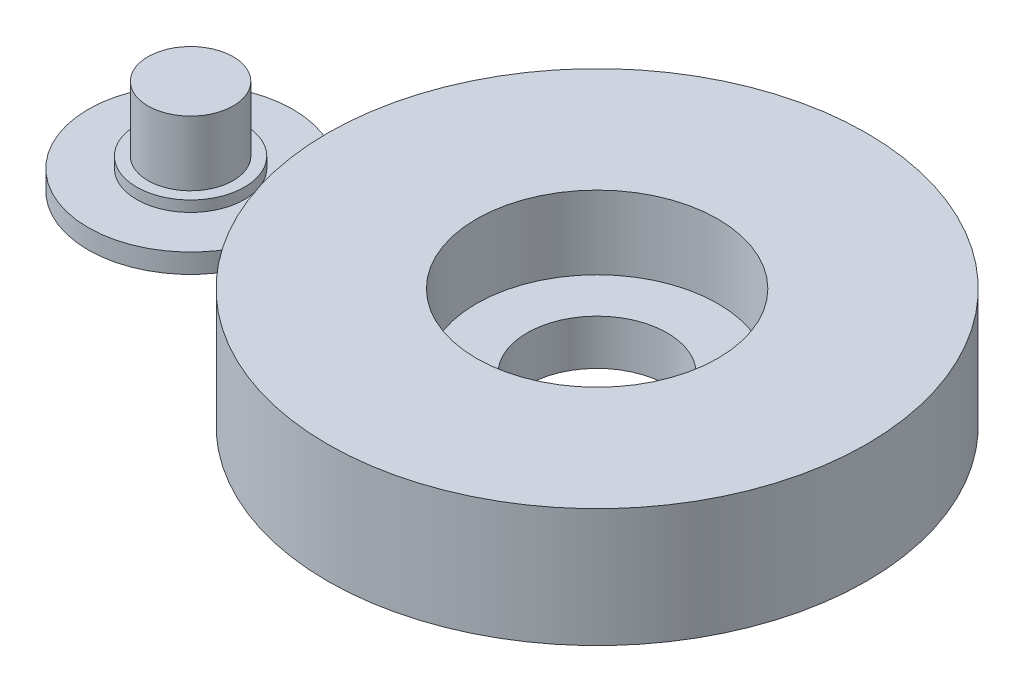
SolidWorks part; units mm, degrees
ref_plane "Front Plane" through (0, 0, 0) normal (0, 0, 1) x (1, 0, 0)
ref_plane "Top Plane" through (0, 0, 0) normal (0, 1, 0) x (1, 0, 0)
ref_plane "Right Plane" through (0, 0, 0) normal (1, 0, 0) x (0, 0, -1)
sketch "Sketch1" plane through (0, 0, 0) normal (0, 1, 0) x (1, 0, 0)
  circle A0 centre (0, 0) radius 9.5
  dimension "D1" = 19
extrude "Boss-Extrude1" add sketch "Sketch1" along normal blind 1.8
sketch "Sketch2" plane through (0, 1.8, 0) normal (0, 1, 0) x (1, 0, 0)
  circle A0 centre (0, 0) radius 3.955
  dimension "D1" = 7.91
extrude "Boss-Extrude2" add sketch "Sketch2" along normal blind 7
sketch "Sketch3" plane through (0, 1.8, 0) normal (0, 1, 0) x (1, 0, 0)
  circle A0 centre (0, 0) radius 5
  dimension "D1" = 10
extrude "Boss-Extrude3" add sketch "Sketch3" along normal blind 1
sketch "Sketch5" plane through (0, 0, 0) normal (0, 1, 0) x (1, 0, 0)
  circle A0 centre (37.7132, 0) radius 25
  dimension "D1" = 50
extrude "Boss-Extrude4" add sketch "Sketch5" along normal blind 11 separate body
sketch "Sketch6" plane through (0, 11, 0) normal (0, 1, 0) x (1, 0, 0)
  circle A0 centre (37.7132, 0) radius 11.2
  dimension "D1" = 22.4
extrude "Cut-Extrude1" cut sketch "Sketch6" against normal blind 6.8
sketch "Sketch7" plane through (0, 4.2, 0) normal (0, 1, 0) x (1, 0, 0)
  circle A0 centre (37.7132, 0) radius 6.5
  dimension "D1" = 13
extrude "Cut-Extrude2" cut sketch "Sketch7" against normal blind 6.8
